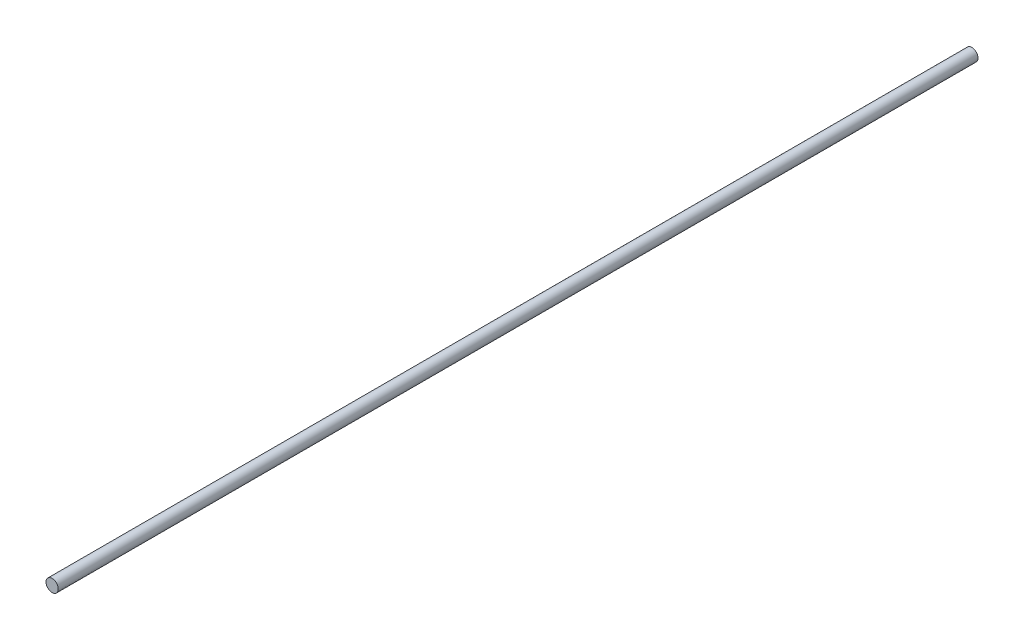
SolidWorks part; units mm, degrees
material "Chrome Stainless Steel"
ref_plane "Front Plane" through (0, 0, 0) normal (0, 0, 1) x (1, 0, 0)
ref_plane "Top Plane" through (0, 0, 0) normal (0, 1, 0) x (1, 0, 0)
ref_plane "Right Plane" through (0, 0, 0) normal (1, 0, 0) x (0, 0, -1)
sketch "Sketch1" plane through (0, 0, 0) normal (0, 0, 1) x (1, 0, 0)
  circle A0 centre (0, 0) radius 3
extrude "Boss-Extrude1" add sketch "Sketch1" along normal blind 450
